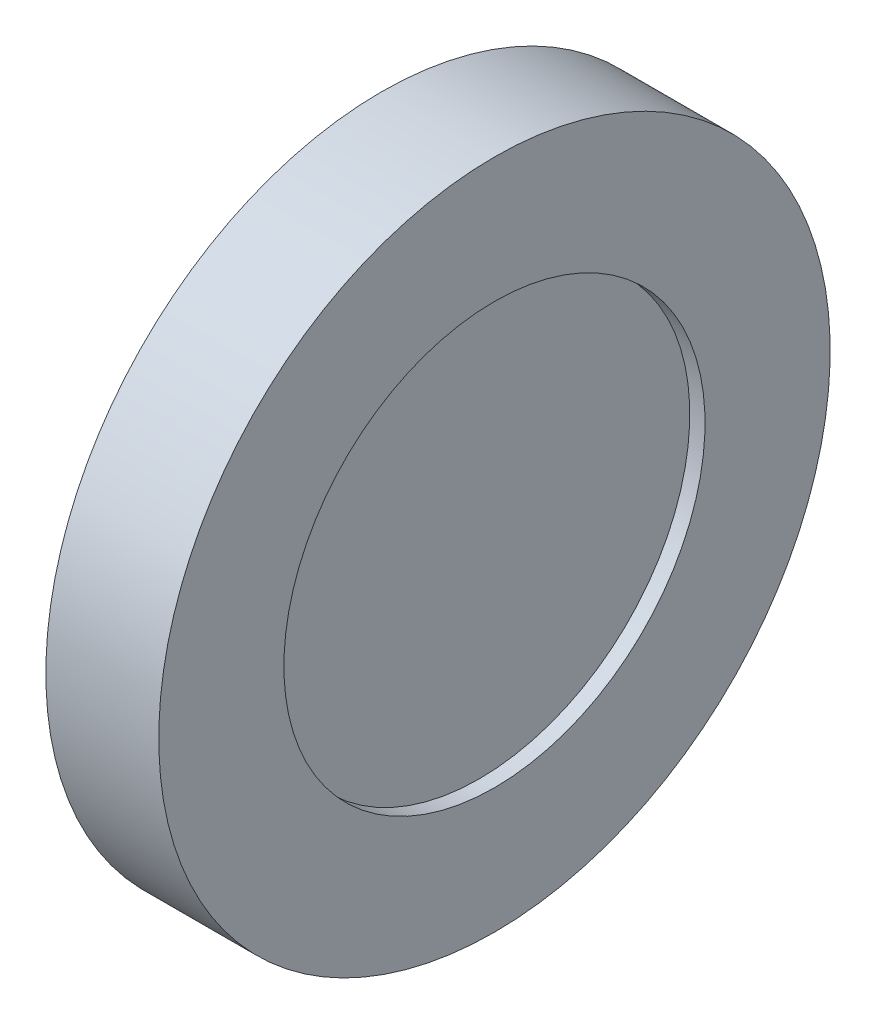
SolidWorks part; units mm, degrees
ref_plane "Front" through (0, 0, 0) normal (0, 0, 1) x (1, 0, 0)
ref_plane "Top" through (0, 0, 0) normal (0, 1, 0) x (1, 0, 0)
ref_plane "Right" through (0, 0, 0) normal (1, 0, 0) x (0, 0, -1)
sketch "Sketch1" plane through (0, 0, 0) normal (0, 0, 1) x (1, 0, 0)
  line L0 (-1.85, 6.9) -> (-1.35, 6.9)
  line L1 (-1.85, 0) -> (1.85, 0)
  line L2 (-1.85, 0) -> (-1.85, 11)
  line L3 (-1.85, 11) -> (1.85, 11)
  line L4 (1.85, 0) -> (1.85, 11)
  line L5 (-1.35, 6.9) -> (-1.35, 0)
  line L6 (1.85, 6.9) -> (1.35, 6.9)
  line L7 (1.35, 6.9) -> (1.35, 0)
  point P4 (0, 0)
  dimension "D1" = 3.7
  dimension "D2" = 11
  dimension "D3" = 6.9
  dimension "D4" = 0.5
revolve "Revolve1" add sketch "Sketch1" angle 360 about L1 region at (0, 5.9185, 0)
